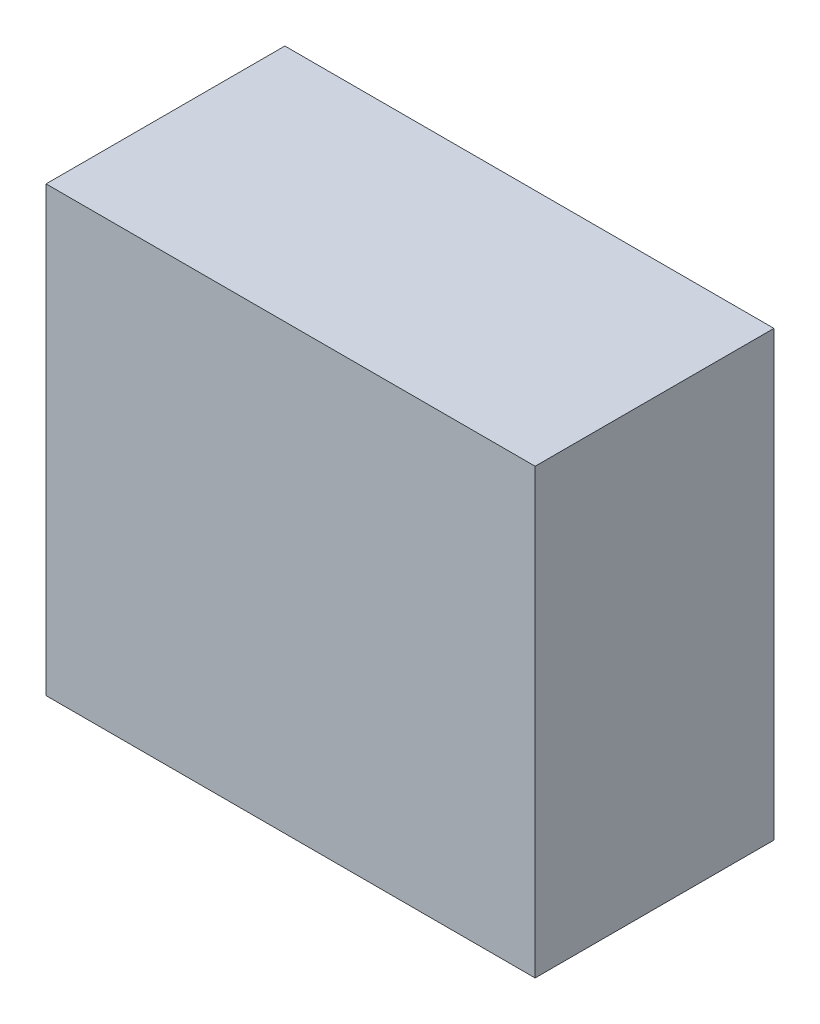
SolidWorks part; units mm, degrees
ref_plane "Front Plane" through (0, 0, 0) normal (0, 0, 1) x (1, 0, 0)
ref_plane "Top Plane" through (0, 0, 0) normal (0, 1, 0) x (1, 0, 0)
ref_plane "Right Plane" through (0, 0, 0) normal (1, 0, 0) x (0, 0, -1)
sketch "Эскиз1" plane through (0, 0, 0) normal (0, 0, 1) x (1, 0, 0)
  line L1 (-12.8, -11.6) -> (12.8, -11.6)
  line L2 (-12.8, -11.6) -> (-12.8, 11.6)
  line L3 (-12.8, 11.6) -> (12.8, 11.6)
  line L4 (12.8, -11.6) -> (12.8, 11.6)
  line L5 (-12.8, -11.6) -> (12.8, 11.6) construction
  line L6 (-12.8, 11.6) -> (12.8, -11.6) construction
  point P0 (0, 0)
  dimension "D1" = 23.2
  dimension "D2" = 25.6
extrude "Бобышка-Вытянуть1" add sketch "Эскиз1" along normal mid plane 12.5
